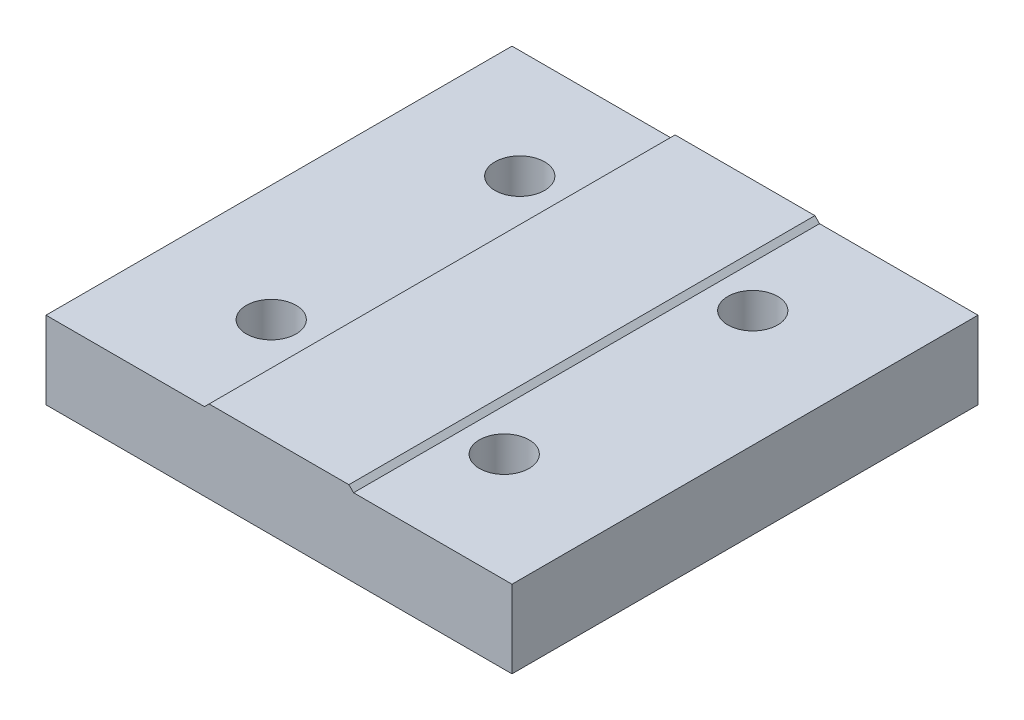
SolidWorks part; units mm, degrees
ref_plane "前视基准面" through (0, 0, 0) normal (0, 0, 1) x (1, 0, 0)
ref_plane "上视基准面" through (0, 0, 0) normal (0, 1, 0) x (1, 0, 0)
ref_plane "右视基准面" through (0, 0, 0) normal (1, 0, 0) x (0, 0, -1)
other "Configuration Table"
sketch "草图1" plane through (0, 0, 0) normal (0, 1, 0) x (1, 0, 0)
  line L1 (0, 0) -> (30, 0)
  line L2 (0, 0) -> (0, -30)
  line L3 (0, -30) -> (30, -30)
  line L4 (30, 0) -> (30, -30)
  circle A0 centre (7.5, -7) radius 1.6
  circle A1 centre (22.5, -7) radius 1.6
  circle A2 centre (22.5, -23) radius 1.6
  circle A3 centre (7.5, -23) radius 1.6
  dimension "D3" = 3.2
  dimension "D1" = 30
  dimension "D2" = 30
  dimension "D6" = 7.5
  dimension "D7" = 7
  dimension "D4" = 2
  dimension "D5" = 2
extrude "凸台-拉伸1" add sketch "草图1" along normal blind 5
sketch "草图2" plane through (0, 5, 0) normal (0, 1, 0) x (1, 0, 0)
  line L8 (30, 0) -> (0, 0) construction
  line L9 (10.2, 0) -> (19.8, 0)
  line L10 (10.2, 0) -> (10.2, -30)
  line L11 (10.2, -30) -> (19.8, -30)
  line L12 (19.8, 0) -> (19.8, -30)
  line L13 (0, -30) -> (30, -30) construction
  line L14 (0, 0) -> (0, -30) construction
  point P8 (15, -30)
  dimension "D1" = 9.6
  dimension "5" = 15
extrude "凸台-拉伸2" add sketch "草图2" along normal blind 0.3
chamfer "倒角2" distance 0.3 angle 45 2 edges at (19.8, 5.3, 15) (10.2, 5.3, 15)
equation "\"D6@草图1\"=15-7.5"
equation "\"D7@草图1\"=15-8"
